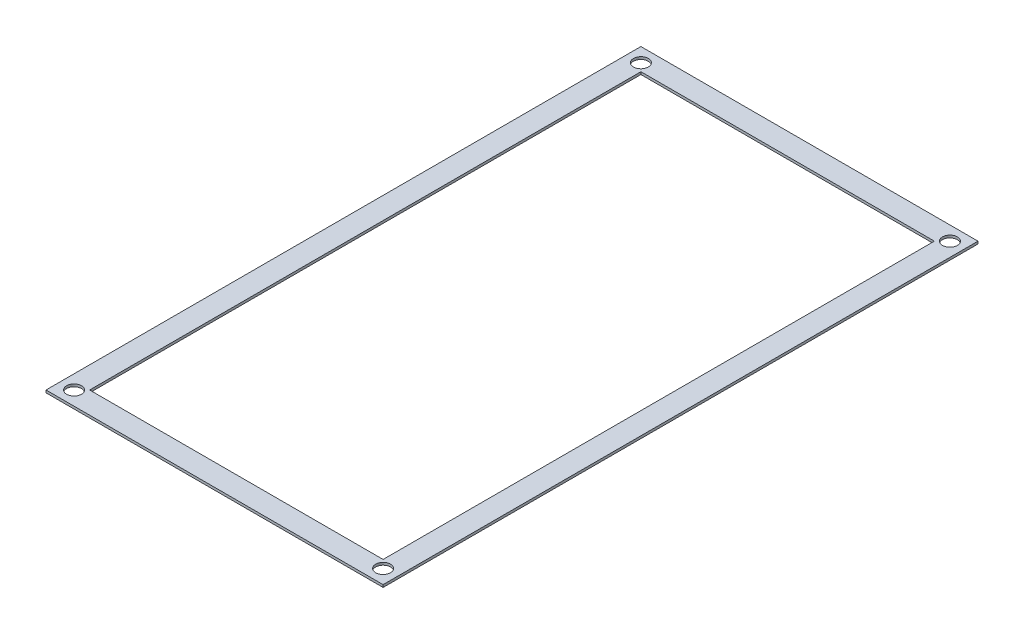
SolidWorks part; units mm, degrees
material "Rubber"
ref_plane "Front Plane" through (0, 0, 0) normal (0, 0, 1) x (1, 0, 0)
ref_plane "Top Plane" through (0, 0, 0) normal (0, 1, 0) x (1, 0, 0)
ref_plane "Right Plane" through (0, 0, 0) normal (1, 0, 0) x (0, 0, -1)
sketch "Sketch3" plane through (0, 0, 0) normal (0, 1, 0) x (1, 0, 0)
  line L1 (-17, 26) -> (-17, 35.8093)
  line L2 (-17, 35.8093) -> (-7.1907, 35.8093)
  line L4 (0, 22.5721) -> (0, 0) construction
  line L6 (-17, 5.8093) -> (17, 5.8093) construction
  line L8 (17, 26) -> (17, -14.3815)
  line L9 (-17, 35.8093) -> (-14.1716, 32.9808) construction
  line L11 (-17, 35.8093) -> (-17, 26)
  line L12 (-7.1907, 35.8093) -> (-17, 35.8093)
  line L13 (17, 35.8093) -> (14.1716, 32.9808) construction
  line L14 (7.1907, 35.8093) -> (17, 35.8093)
  line L15 (17, 35.8093) -> (17, 26)
  line L16 (17, 35.8093) -> (7.1907, 35.8093)
  line L17 (17, 26) -> (17, 35.8093)
  line L18 (17, -24.1907) -> (14.1716, -21.3623) construction
  line L19 (-17, -24.1907) -> (-14.1716, -21.3623) construction
  line L20 (17, -14.3815) -> (17, -24.1907)
  line L21 (17, -24.1907) -> (7.1907, -24.1907)
  line L22 (17, -24.1907) -> (17, -14.3815)
  line L23 (7.1907, -24.1907) -> (17, -24.1907)
  line L24 (-7.1907, -24.1907) -> (-17, -24.1907)
  line L25 (-17, -24.1907) -> (-17, -14.3815)
  line L26 (-17, -24.1907) -> (-7.1907, -24.1907)
  line L27 (-17, -14.3815) -> (-17, -24.1907)
  line L31 (7.1907, -24.1907) -> (-7.1907, -24.1907)
  line L32 (-17, -14.3815) -> (-17, 26)
  line L33 (-7.1907, 35.8093) -> (7.1907, 35.8093)
  circle A1 centre (-15.5858, 34.3951) radius 0.75
  circle A6 centre (15.5858, 34.3951) radius 0.75
  circle A7 centre (15.5858, -22.7765) radius 0.75
  circle A10 centre (-15.5858, -22.7765) radius 0.75
  point P3 (-17, 5.8093)
  point P11 (0, 30)
  dimension "D2" = 1.5
  dimension "D1" = 1.4142
  dimension "D3" = 30
  dimension "D4" = 17
  dimension "D5" = 35.8093
extrude "Boss-Extrude1" add sketch "Sketch3" along normal blind 0.25 contours L33 L2 L1 L32 L25 L24 L31 L21 L20 L8 L15 L14 A6 A1 A7 A10 region at (0, 0, -5.8093)
sketch "Sketch4" plane through (0, 0.25, 0) normal (0, 1, 0) x (1, 0, 0)
  line L0 (-17, -24.1907) -> (-17, 35.8093) construction
  line L1 (-17, 35.8093) -> (17, 35.8093) construction
  line L2 (17, 35.8093) -> (17, -24.1907) construction
  line L3 (14.8, -21.9907) -> (-14.8, -21.9907)
  line L4 (14.8, -21.9907) -> (14.8, 33.6093)
  line L5 (14.8, 33.6093) -> (-14.8, 33.6093)
  line L6 (-14.8, -21.9907) -> (-14.8, 33.6093)
  line L7 (14.8, -21.9907) -> (-14.8, 33.6093) construction
  line L8 (14.8, 33.6093) -> (-14.8, -21.9907) construction
  line L9 (17, -24.1907) -> (-17, -24.1907) construction
  point P0 (-17, 5.8093)
  point P1 (0, 35.8093)
  point P4 (0, 5.8093)
  dimension "D1" = 2.2
  dimension "D2" = 2.2
  dimension "D3" = 2.2
  dimension "D4" = 2.2
extrude "Cut-Extrude1" cut sketch "Sketch4" against normal blind 10
